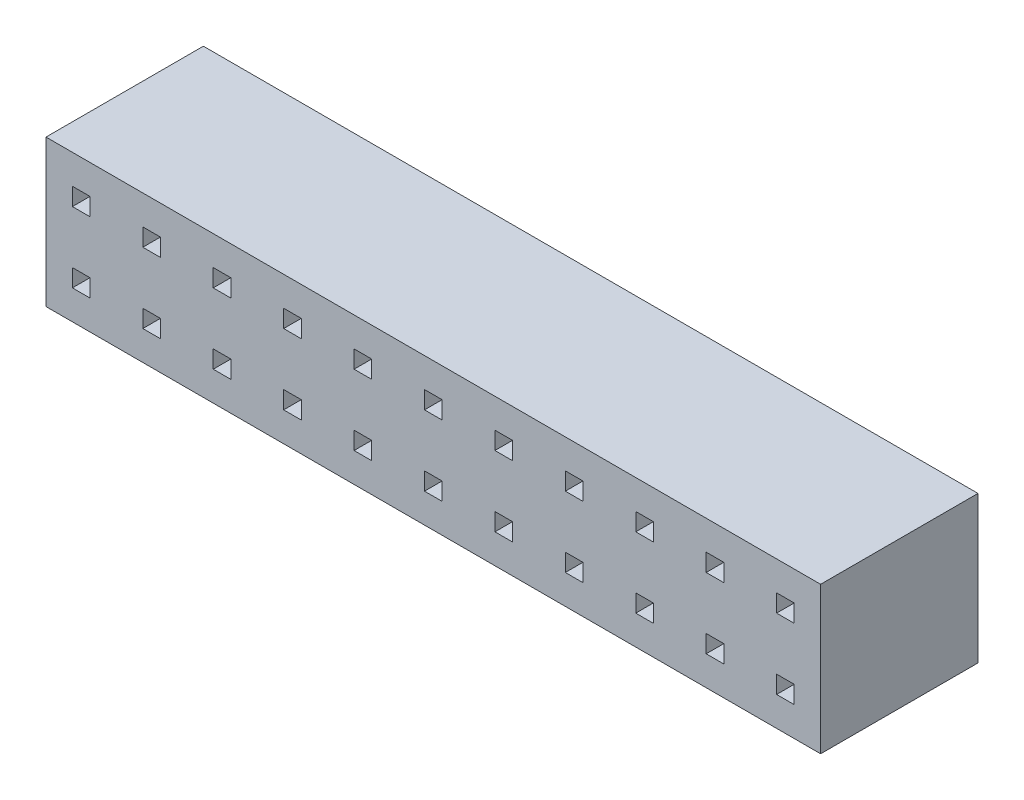
SolidWorks part; units mm, degrees
ref_plane "Front Plane" through (0, 0, 0) normal (0, 0, 1) x (1, 0, 0)
ref_plane "Top Plane" through (0, 0, 0) normal (0, 1, 0) x (1, 0, 0)
ref_plane "Right Plane" through (0, 0, 0) normal (1, 0, 0) x (0, 0, -1)
sketch "Sketch1" plane through (0, 0, 0) normal (0, 0, 1) x (1, 0, 0)
  line L1 (0, -0.085) -> (22, -0.085)
  line L2 (0, -0.085) -> (0, 4.085)
  line L3 (0, 4.085) -> (22, 4.085)
  line L4 (22, -0.085) -> (22, 4.085)
extrude "Boss-Extrude1" add sketch "Sketch1" along normal blind 4.47
sketch "Sketch2" plane through (0, 0, 4.47) normal (0, 0, 1) x (1, 0, 0)
  line L1 (0.75, 0.75) -> (1.25, 0.75)
  line L2 (0.75, 0.75) -> (0.75, 1.25)
  line L3 (0.75, 1.25) -> (1.25, 1.25)
  line L4 (1.25, 0.75) -> (1.25, 1.25)
  line L88 (2.75, 0.75) -> (3.25, 0.75)
  line L89 (2.75, 0.75) -> (2.75, 1.25)
  line L90 (2.75, 1.25) -> (3.25, 1.25)
  line L91 (3.25, 0.75) -> (3.25, 1.25)
  line L92 (4.75, 0.75) -> (5.25, 0.75)
  line L93 (4.75, 0.75) -> (4.75, 1.25)
  line L94 (4.75, 1.25) -> (5.25, 1.25)
  line L95 (5.25, 0.75) -> (5.25, 1.25)
  line L96 (6.75, 0.75) -> (7.25, 0.75)
  line L97 (6.75, 0.75) -> (6.75, 1.25)
  line L98 (6.75, 1.25) -> (7.25, 1.25)
  line L99 (7.25, 0.75) -> (7.25, 1.25)
  line L100 (8.75, 0.75) -> (9.25, 0.75)
  line L101 (8.75, 0.75) -> (8.75, 1.25)
  line L102 (8.75, 1.25) -> (9.25, 1.25)
  line L103 (9.25, 0.75) -> (9.25, 1.25)
  line L104 (10.75, 0.75) -> (11.25, 0.75)
  line L105 (10.75, 0.75) -> (10.75, 1.25)
  line L106 (10.75, 1.25) -> (11.25, 1.25)
  line L107 (11.25, 0.75) -> (11.25, 1.25)
  line L108 (12.75, 0.75) -> (13.25, 0.75)
  line L109 (12.75, 0.75) -> (12.75, 1.25)
  line L110 (12.75, 1.25) -> (13.25, 1.25)
  line L111 (13.25, 0.75) -> (13.25, 1.25)
  line L112 (14.75, 0.75) -> (15.25, 0.75)
  line L113 (14.75, 0.75) -> (14.75, 1.25)
  line L114 (14.75, 1.25) -> (15.25, 1.25)
  line L115 (15.25, 0.75) -> (15.25, 1.25)
  line L116 (16.75, 0.75) -> (17.25, 0.75)
  line L117 (16.75, 0.75) -> (16.75, 1.25)
  line L118 (16.75, 1.25) -> (17.25, 1.25)
  line L119 (17.25, 0.75) -> (17.25, 1.25)
  line L120 (18.75, 0.75) -> (19.25, 0.75)
  line L121 (18.75, 0.75) -> (18.75, 1.25)
  line L122 (18.75, 1.25) -> (19.25, 1.25)
  line L123 (19.25, 0.75) -> (19.25, 1.25)
  line L124 (20.75, 0.75) -> (21.25, 0.75)
  line L125 (20.75, 0.75) -> (20.75, 1.25)
  line L126 (20.75, 1.25) -> (21.25, 1.25)
  line L127 (21.25, 0.75) -> (21.25, 1.25)
  line L128 (0.75, 2.75) -> (1.25, 2.75)
  line L129 (0.75, 2.75) -> (0.75, 3.25)
  line L130 (0.75, 3.25) -> (1.25, 3.25)
  line L131 (1.25, 2.75) -> (1.25, 3.25)
  line L132 (2.75, 2.75) -> (3.25, 2.75)
  line L133 (2.75, 2.75) -> (2.75, 3.25)
  line L134 (2.75, 3.25) -> (3.25, 3.25)
  line L135 (3.25, 2.75) -> (3.25, 3.25)
  line L136 (4.75, 2.75) -> (5.25, 2.75)
  line L137 (4.75, 2.75) -> (4.75, 3.25)
  line L138 (4.75, 3.25) -> (5.25, 3.25)
  line L139 (5.25, 2.75) -> (5.25, 3.25)
  line L140 (6.75, 2.75) -> (7.25, 2.75)
  line L141 (6.75, 2.75) -> (6.75, 3.25)
  line L142 (6.75, 3.25) -> (7.25, 3.25)
  line L143 (7.25, 2.75) -> (7.25, 3.25)
  line L144 (8.75, 2.75) -> (9.25, 2.75)
  line L145 (8.75, 2.75) -> (8.75, 3.25)
  line L146 (8.75, 3.25) -> (9.25, 3.25)
  line L147 (9.25, 2.75) -> (9.25, 3.25)
  line L148 (10.75, 2.75) -> (11.25, 2.75)
  line L149 (10.75, 2.75) -> (10.75, 3.25)
  line L150 (10.75, 3.25) -> (11.25, 3.25)
  line L151 (11.25, 2.75) -> (11.25, 3.25)
  line L152 (12.75, 2.75) -> (13.25, 2.75)
  line L153 (12.75, 2.75) -> (12.75, 3.25)
  line L154 (12.75, 3.25) -> (13.25, 3.25)
  line L155 (13.25, 2.75) -> (13.25, 3.25)
  line L156 (14.75, 2.75) -> (15.25, 2.75)
  line L157 (14.75, 2.75) -> (14.75, 3.25)
  line L158 (14.75, 3.25) -> (15.25, 3.25)
  line L159 (15.25, 2.75) -> (15.25, 3.25)
  line L160 (16.75, 2.75) -> (17.25, 2.75)
  line L161 (16.75, 2.75) -> (16.75, 3.25)
  line L162 (16.75, 3.25) -> (17.25, 3.25)
  line L163 (17.25, 2.75) -> (17.25, 3.25)
  line L164 (18.75, 2.75) -> (19.25, 2.75)
  line L165 (18.75, 2.75) -> (18.75, 3.25)
  line L166 (18.75, 3.25) -> (19.25, 3.25)
  line L167 (19.25, 2.75) -> (19.25, 3.25)
  line L168 (20.75, 2.75) -> (21.25, 2.75)
  line L169 (20.75, 2.75) -> (20.75, 3.25)
  line L170 (20.75, 3.25) -> (21.25, 3.25)
  line L171 (21.25, 2.75) -> (21.25, 3.25)
  dimension "D2" = 2
  dimension "D1" = 11
extrude "Cut-Extrude1" cut sketch "Sketch2" against normal blind 4.47
ref_plane "Plane1" through (0.9828, -2.2931, 0) normal (0.3939, -0.9191, 0) x (-0.9191, -0.3939, 0)
ref_plane "Plane2" through (2.431, 5.6724, 0) normal (-0.3939, -0.9191, 0) x (-0.9191, 0.3939, 0)
ref_axis "Axis1" through (11, 2, -8.6494) along (0, 0, 1)
